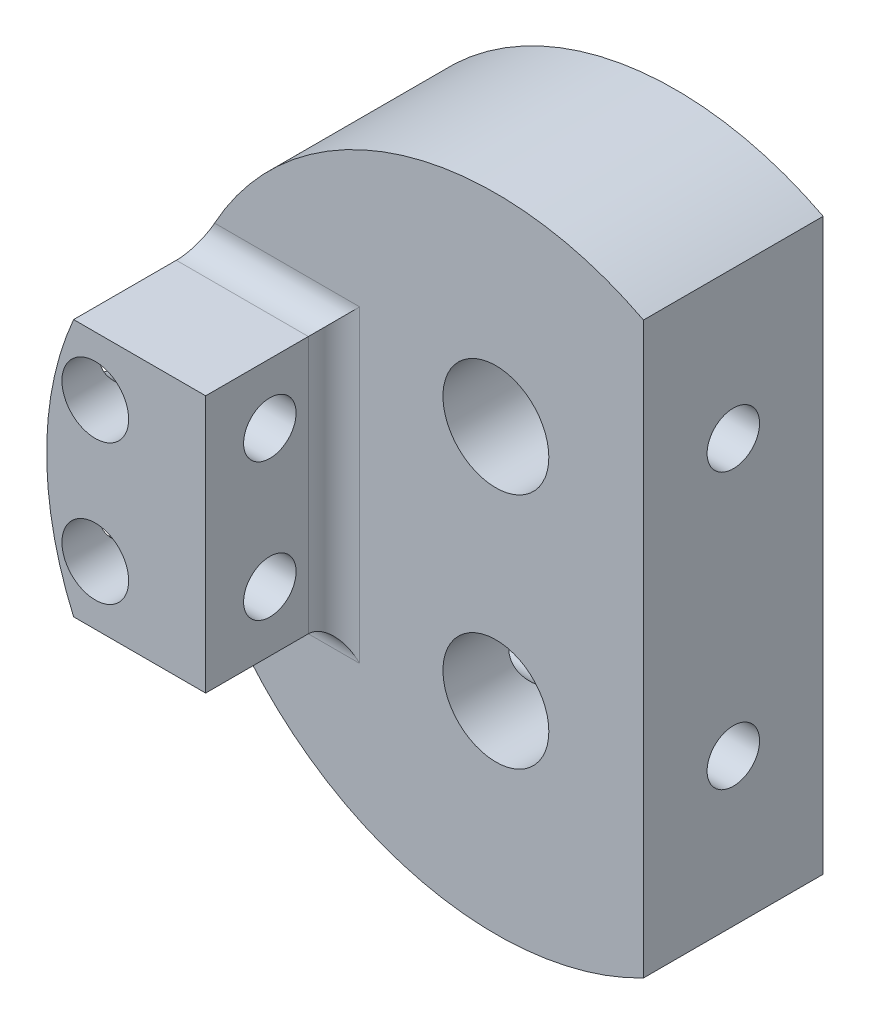
SolidWorks part; units mm, degrees
ref_plane "Front Plane" through (0, 0, 0) normal (1, 0, 0) x (0, 1, 0)
ref_plane "Top Plane" through (0, 0, 0) normal (0, 0, 1) x (0, 1, 0)
ref_plane "Right Plane" through (0, 0, 0) normal (0, 1, 0) x (-1, 0, 0)
sketch "Sketch1" plane through (0, 0, 0) normal (0, 0, 1) x (0, 1, 0)
  line L0 (-23.5, 8.5294) -> (23.5, 8.5294) construction
  line L1 (0, 25) -> (0, -25) construction
  circle A0 centre (0, 0) radius 25
  dimension "D1" = 50
extrude "Boss-Extrude1" add sketch "Sketch1" along normal blind 14
sketch "Sketch2" plane through (0, 0, 14) normal (0, 0, 1) x (0, -1, 0)
  line L0 (0, -25) -> (0, 25) construction
  line L1 (-23.5, -8.5294) -> (23.5, -8.5294)
  arc A0 (-23.5, -8.5294) -> (23.5, -8.5294) centre (0, 0) ccw
extrude "Boss-Extrude2" add sketch "Sketch2" along normal blind 10
sketch "Sketch3" plane through (0, 0, 24) normal (0, 0, 1) x (1, 0, 0)
  line L0 (-20.1083, 0) -> (-20.1083, -3.0956) construction
  line L1 (-25, 0) -> (25, 0) construction
  line L2 (-8.5294, 0) -> (-25, 0) construction
  line L3 (-8.5294, -23.5) -> (-8.5294, 23.5) construction
  line L4 (-21.2113, -2.85) -> (-21.2113, 0) construction
  circle A1 centre (-21.2113, -5.45) radius 2.6
  circle A2 centre (-21.2113, 5.45) radius 2.6
  dimension "D1" = 2.85
extrude "2.6 mm for linear rods" cut sketch "Sketch3" against normal through all
sketch "Sketch4" plane through (0, 0, 14) normal (0, 0, 1) x (1, 0, 0)
  line L0 (0, -25) -> (0, 25) construction
  line L1 (25, 0) -> (-25, 0) construction
  line L2 (0, 0) -> (0, -5.125) construction
  line L3 (0, -5.125) -> (0, 0)
  circle A0 centre (0, 0) radius 25 construction
  circle A1 centre (0, -9.25) radius 4.125
  circle A2 centre (0, 9.25) radius 4.125
  dimension "D1" = 8.25
extrude "8.25 mm for linear rods" cut sketch "Sketch4" against normal through all contours A2 | A1 region at (0, -9.25, 14) region at (0, 9.25, 14)
sketch "Sketch5" plane through (-8.5294, 0, 0) normal (1, 0, 0) x (0, 1, 0)
  line L0 (-23.5, 19) -> (23.5, 19) construction
  line L1 (-23.5, 24) -> (-23.5, 14) construction
  line L2 (23.5, 24) -> (23.5, 14) construction
  line L3 (0, 24) -> (0, 14) construction
  line L4 (-23.5, 24) -> (23.5, 24) construction
  line L5 (25, 14) -> (-25, 14) construction
  line L6 (-8.05, 24) -> (-2.85, 24) construction
  line L7 (-13.375, 7) -> (-8.05, 7) construction
  line L8 (-13.375, 14) -> (-13.375, 0) construction
  line L9 (-8.05, 24) -> (-8.05, 0) construction
  circle A0 centre (-5.35, 19) radius 2.045
  circle A1 centre (5.35, 19) radius 2.045
  circle A2 centre (-10.7125, 7) radius 2.045
  circle A3 centre (10.7125, 7) radius 2.045
  dimension "D1" = 4.09
extrude "M3 Hole for heatset" cut sketch "Sketch5" against normal through all both and the other way through all contours A0 | A1 | A2 | A3 | A0 | A1 | A2 | A3 region at (-8.5294, -5.35, 19) region at (-8.5294, 5.35, 19) region at (-8.5294, -10.7125, 7) region at (-8.5294, 10.7125, 7)
sketch "Sketch7" plane through (0, 0, 24) normal (0, 0, 1) x (1, 0, 0)
  line L0 (-22.8997, 10.0301) -> (-12.6113, 10.0301)
  line L1 (-8.5294, -23.5) -> (-8.5294, 23.5) construction
  line L2 (-8.5294, 10.0301) -> (-8.5294, 23.5)
  line L3 (-25, 0) -> (-8.5294, 0) construction
  line L4 (-8.5294, -10.0301) -> (-8.5294, -23.5)
  line L5 (-22.8997, -10.0301) -> (-12.6113, -10.0301)
  line L6 (-8.5294, 10.0301) -> (-8.5294, -10.0301)
  line L7 (-18.6113, -5.45) -> (-12.6113, -5.45) construction
  line L8 (-12.6113, 10.0301) -> (-12.6113, -10.0301)
  arc A0 (-22.8997, 10.0301) -> (-8.6579, 23.453) centre (0, 0) cw
  arc A1 (-22.8997, -10.0301) -> (-8.6579, -23.453) centre (0, 0) ccw
  circle A2 centre (-21.2113, -5.45) radius 2.6 construction
  arc M4 (-8.5294, 23.5) -> (-8.5294, -23.5) centre (0, 0) ccw
  line M5 (-8.5294, -23.5) -> (-8.5294, 23.5)
  dimension "D1" = 6
extrude "Cut-Extrude5" cut sketch "Sketch7" against normal blind 10 contours L0 L8 L5 M4 M5 region at (-16.8097, 17.8354, 24)
sketch "Sketch8" plane through (0, 0, 14) normal (0, 0, 1) x (1, 0, 0)
  line L0 (-4, 9.25) -> (4, 9.25)
  line L1 (4, 24.6779) -> (4, -24.6779) construction
  circle A0 centre (0, 9.25) radius 4.125 construction
  circle A1 centre (0, 0) radius 25 construction
  dimension "D1" = 8
ref_plane "Plane1" through (4, 0, 0) normal (-1, 0, 0) x (0, -1, 0)
sketch "Sketch9" plane through (4, 0, 0) normal (-1, 0, 0) x (0, -1, 0)
  line L1 (-25.9824, 15.6208) -> (26.3443, 15.6208)
  line L2 (-25.9824, 15.6208) -> (-25.9824, -2.6899)
  line L3 (-25.9824, -2.6899) -> (26.3443, -2.6899)
  line L4 (26.3443, 15.6208) -> (26.3443, -2.6899)
  line L5 (-25.9824, 15.6208) -> (26.3443, -2.6899) construction
  line L6 (-25.9824, -2.6899) -> (26.3443, 15.6208) construction
  point P4 (0.1809, 6.4654)
extrude "Cut-Extrude6" cut sketch "Sketch9" against normal blind 21 from offset 7.5 offset against normal yes
sketch "Sketch10" plane through (0, 0, 14) normal (0, 0, 1) x (1, 0, 0)
  line L0 (-4.85, -10.1) -> (-4.85, 10.1)
  line L1 (0, 0) -> (12.414, 0) construction
  line L2 (-15.1, -10.1) -> (-15.1, 10.1)
  line L4 (-15.1, 0) -> (-4.85, 0)
  line L7 (0, -25) -> (0, 25) construction
  line L9 (4, -9.25) -> (4.5, -9.25)
  line L11 (-25, 0) -> (25, 0) construction
  circle A0 centre (5.099, -18.02) radius 4.1
  arc A1 (-15.1, -10.1) -> (-4.85, -10.1) centre (-9.975, -10.1) ccw
  arc A4 (-15.1, 10.1) -> (-4.85, 10.1) centre (-9.975, 10.1) cw
  circle A5 centre (0, 0) radius 25 construction
  circle A8 centre (6.207, 0) radius 4.1
  circle A9 centre (5.099, 18.02) radius 4.1
  line M26 (-22.8997, 10.0301) -> (-12.6113, 10.0301)
  line M27 (-12.6113, 10.0301) -> (-12.6113, -10.0301)
  line M28 (-12.6113, -10.0301) -> (-22.8997, -10.0301)
  dimension "D2" = 10.25
  dimension "D1" = 8.2
  dimension "D3" = 8.2
extrude "Magnet Slots" cut sketch "Sketch10" along direction (0, 0, 1) on the side of the normal blind 4 from offset 13.8 contours L2 A1 L0 L4 M27 M28 | A0 | A8 | A9 | A4 L2 L4 L0 M26 M27 | L2 L4 M27 M26 | L4 L2 M28 M27 region at (-9.1665, -7.5451, 14) region at (-9.1665, 7.5451, 14) region at (-13.8556, -5.0151, 14) region at (-13.8556, 5.0151, 14) region at (5.099, -18.02, 14) region at (6.207, 0, 14) region at (5.099, 18.02, 14) offset against normal yes
fillet "Fillet1" radius 2 3 edges at (-17.7555, 10.0301, 14) (-12.6113, 0, 14) (-17.7555, -10.0301, 14)
